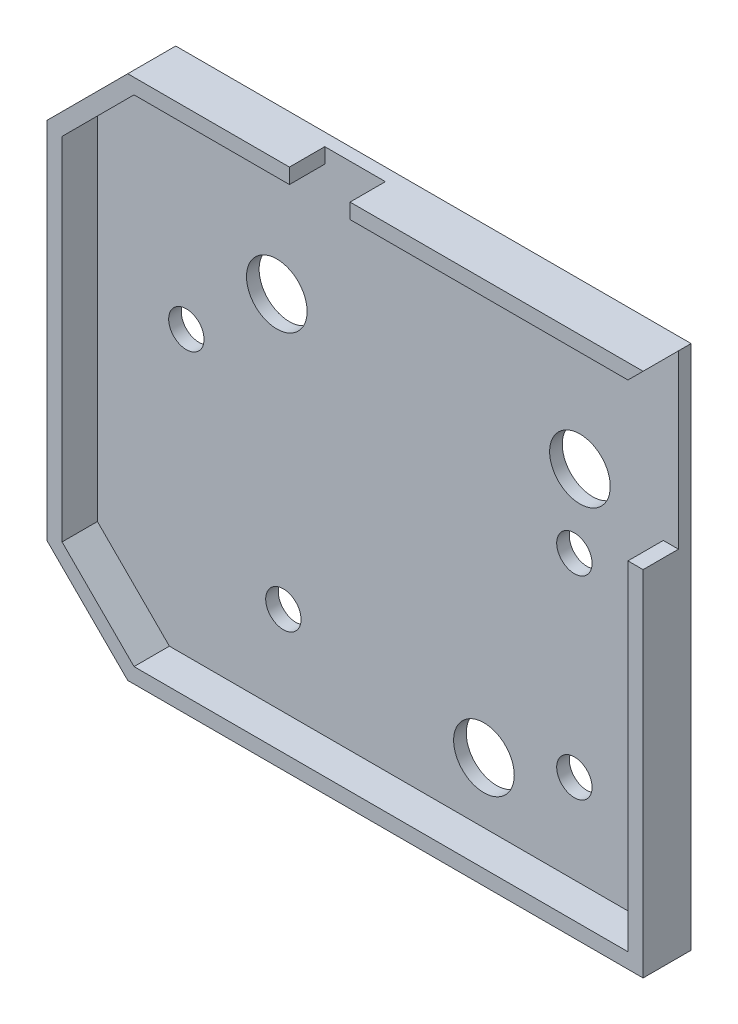
SolidWorks part; units mm, degrees
material "Delrin 2700 NC010, copolymère d'acétal à faible viscosité (SS)"
ref_plane "Plan de face" through (0, 0, 0) normal (0, 0, 1) x (1, 0, 0)
ref_plane "Plan de dessus" through (0, 0, 0) normal (0, 1, 0) x (1, 0, 0)
ref_plane "Plan de droite" through (0, 0, 0) normal (1, 0, 0) x (0, 0, -1)
sketch "Esquisse1" plane through (0, 0, 0) normal (0, 0, 1) x (1, 0, 0)
  line L0 (0, -85) -> (16, -101)
  line L4 (118, 3) -> (118, -101)
  line L5 (16, 3) -> (0, -13)
  line L7 (118, 3) -> (16, 3)
  line L8 (0, -13) -> (0, -85)
  line L9 (16, -101) -> (118, -101)
  dimension "D1" = 104
  dimension "D2" = 118
  dimension "D3" = 16
  dimension "D4" = 16
  dimension "D5" = 16
  dimension "D6" = 16
extrude "Boss.-Extru.1" add sketch "Esquisse1" along normal blind 2.5
sketch "Esquisse2" plane through (0, 0, 2.5) normal (0, 0, 1) x (1, 0, 0)
  line L0 (0, -13) -> (0, -85) construction
  line L1 (3, 0) -> (115, 0) construction
  line L2 (3, 0) -> (3, -98) construction
  line L3 (3, -98) -> (115, -98) construction
  line L4 (115, 0) -> (115, -98) construction
  line L5 (16, -101) -> (118, -101) construction
  line L6 (118, -101) -> (118, 3) construction
  line L7 (118, 3) -> (16, 3) construction
  line L8 (115, -31) -> (118, -31)
  line L9 (3, -83.7574) -> (17.2426, -98)
  line L10 (0, -85) -> (16, -101) construction
  line L11 (3, -14.2426) -> (17.2426, 0)
  line L12 (16, 3) -> (0, -13) construction
  line L14 (3, -14.2426) -> (3, -83.7574)
  line L15 (17.2426, -98) -> (115, -98)
  line L16 (118, 3) -> (118, -101) construction
  line L17 (118, -101) -> (16, -101)
  line L18 (16, -101) -> (0, -85)
  line L19 (0, -85) -> (0, -13)
  line L20 (0, -13) -> (16, 3)
  line L22 (115, 0) -> (118, 3)
  line L23 (115, -98) -> (115, -31)
  line L24 (118, -31) -> (118, -101)
  line L25 (48, 0) -> (48, 3)
  line L26 (60, 0) -> (60, 3)
  line L27 (17.2426, 0) -> (48, 0)
  line L28 (48, 3) -> (16, 3)
  line L29 (60, 3) -> (118, 3)
  line L30 (115, 0) -> (60, 0)
  point P33 (48, 0)
  point P34 (60, 0)
  dimension "D1" = 3
  dimension "D2" = 3
  dimension "D3" = 3
  dimension "D4" = 3
  dimension "D5" = 3
  dimension "D6" = 3
  dimension "D7" = 70
  dimension "D8" = 45
  dimension "D9" = 12
extrude "Boss.-Extru.2" add sketch "Esquisse2" along normal blind 7
sketch "Esquisse3" plane through (0, 0, 2.5) normal (0, 0, 1) x (1, 0, 0)
  line L0 (115, -31) -> (115, -98) construction
  line L2 (3, -83.7574) -> (3, -14.2426) construction
  line L3 (115, -31) -> (115, -98) construction
  line L4 (115, -98) -> (17.2426, -98) construction
  line L5 (60, 3) -> (48, 3) construction
  circle A0 centre (98.5, -27) radius 6
  circle A1 centre (38.5, -27) radius 6
  circle A2 centre (79.5, -86) radius 6
  circle A3 centre (97.4, -42) radius 3.5
  circle A4 centre (20.6, -42) radius 3.5
  circle A5 centre (39.8, -80.4) radius 3.5
  circle A6 centre (97.4, -80.4) radius 3.5
  dimension "D1" = 16.5
  dimension "D2" = 30
  dimension "D3" = 30
  dimension "D4" = 35.5
  dimension "D5" = 35.5
  dimension "D6" = 12
  dimension "D8" = 17.6
  dimension "D9" = 76.8
  dimension "D10" = 57.6
  dimension "D11" = 17.6
  dimension "D13" = 38.4
extrude "Enlèv. mat.-Extru.1" cut sketch "Esquisse3" against normal blind 10
